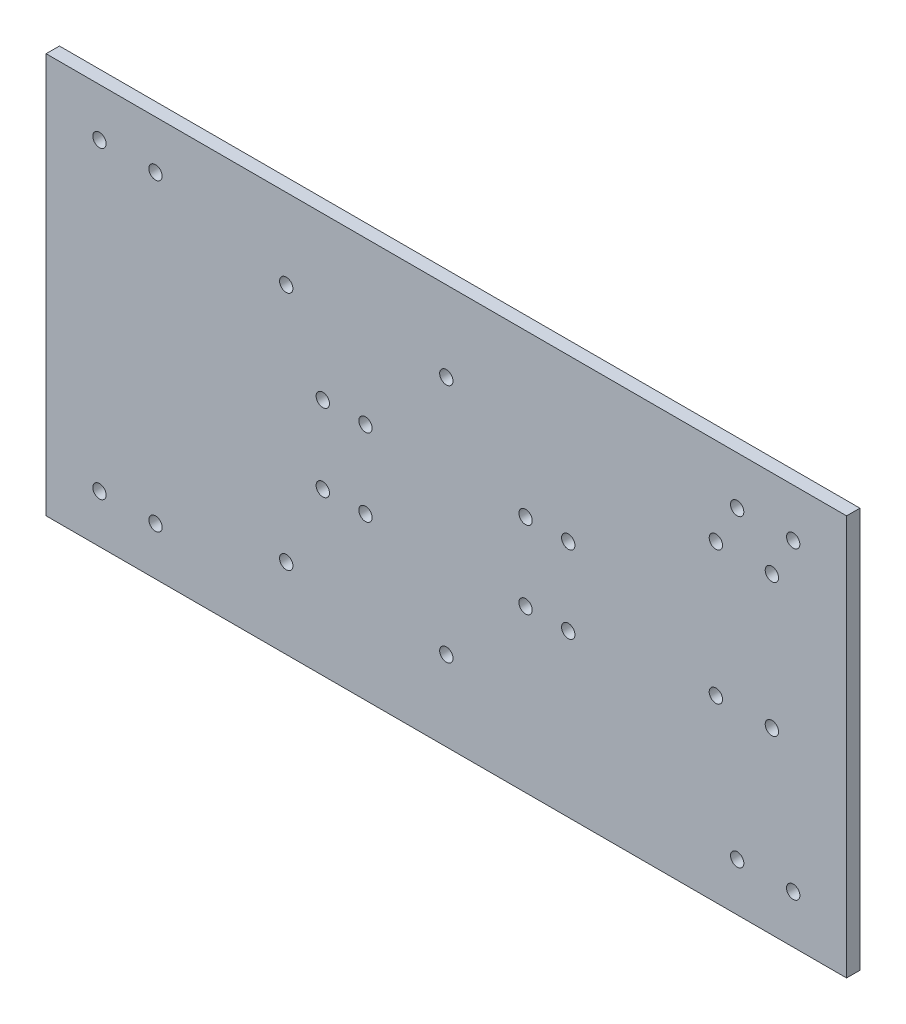
SolidWorks part; units mm, degrees
ref_plane "Plan de face" through (0, 0, 0) normal (0, 0, 1) x (1, 0, 0)
ref_plane "Plan de dessus" through (0, 0, 0) normal (0, 1, 0) x (1, 0, 0)
ref_plane "Plan de droite" through (0, 0, 0) normal (1, 0, 0) x (0, 0, -1)
sketch "Esquisse1" plane through (0, 0, 0) normal (0, 0, 1) x (1, 0, 0)
  line L1 (0, 0) -> (300, 0)
  line L2 (0, 0) -> (0, 150)
  line L3 (0, 150) -> (300, 150)
  line L4 (300, 0) -> (300, 150)
  circle A0 centre (150, 30) radius 2.5
  circle A1 centre (150, 120) radius 2.5
  circle A2 centre (103.7, 89.5) radius 2.5
  circle A3 centre (103.7, 60.5) radius 2.5
  circle A4 centre (119.7, 89.5) radius 2.5
  circle A5 centre (119.7, 60.5) radius 2.5
  circle A6 centre (90, 120) radius 2.5
  circle A7 centre (90, 30) radius 2.5
  circle A8 centre (179.7, 89.5) radius 2.5
  circle A11 centre (179.7, 60.5) radius 2.5
  circle A12 centre (195.7, 89.5) radius 2.5
  circle A13 centre (195.7, 60.5) radius 2.5
  circle A22 centre (251.014, 67.15) radius 2.5
  circle A23 centre (272.014, 67.15) radius 2.5
  circle A24 centre (251.014, 117.15) radius 2.5
  circle A25 centre (272.014, 117.15) radius 2.5
  dimension "D3" = 150
  dimension "D46" = 82.85
  dimension "D47" = 82.85
  dimension "D49" = 21
  dimension "D1" = 300
  dimension "D2" = 150
  dimension "D4" = 150
  dimension "D7" = 90
  dimension "D8" = 30
  dimension "D11" = 30.5
  dimension "D12" = 30.5
  dimension "D13" = 46.3
  dimension "D14" = 46.3
  dimension "D17" = 16
  dimension "D18" = 16
  dimension "D19" = 30.5
  dimension "D20" = 30.5
  dimension "D22" = 60
  dimension "D23" = 30
  dimension "D25" = 60
  dimension "D26" = 30
  dimension "D27" = 60
  dimension "D28" = 60
  dimension "D29" = 16
  dimension "D30" = 16
  dimension "D31" = 0
  dimension "D32" = 0
  dimension "D33" = 0
  dimension "D34" = 0
  dimension "D48" = 21
  dimension "D50" = 50
extrude "Boss.-Extru.1" add sketch "Esquisse1" along normal blind 5
sketch "Esquisse2" plane through (0, 0, 5) normal (0, 0, 1) x (1, 0, 0)
  line L0 (300, 0) -> (300, 150) construction
  line L1 (300, 150) -> (0, 150) construction
  line L2 (0, 0) -> (300, 0) construction
  line L3 (0, 150) -> (0, 0) construction
  circle A1 centre (280, 132) radius 2.5
  circle A3 centre (280, 18) radius 2.5
  circle A4 centre (20, 132) radius 2.5
  circle A6 centre (20, 18) radius 2.5
  circle A8 centre (259, 132) radius 2.5
  circle A9 centre (259, 18) radius 2.5
  circle A10 centre (41, 18) radius 2.5
  circle A11 centre (41, 132) radius 2.5
  dimension "D1" = 21
  dimension "D6" = 18
  dimension "D8" = 21
  dimension "D2" = 20
  dimension "D3" = 18
  dimension "D4" = 20
  dimension "D5" = 18
  dimension "D7" = 20
  dimension "D9" = 18
extrude "Enlèv. mat.-Extru.1" cut sketch "Esquisse2" against normal blind 10
